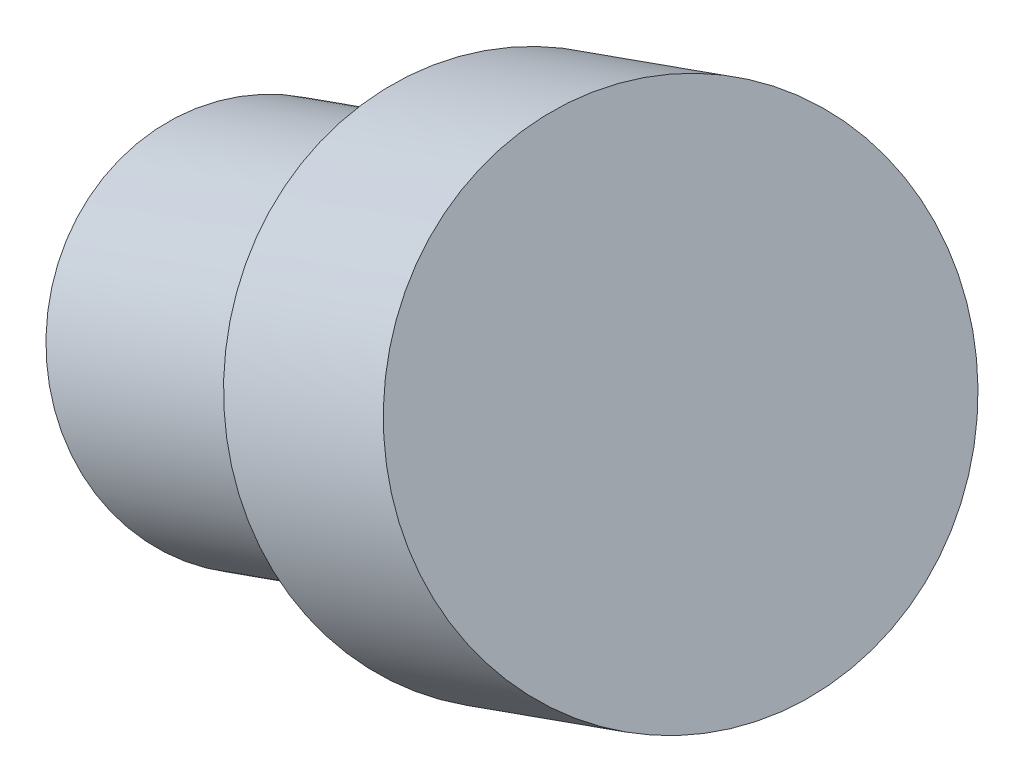
SolidWorks part; units mm, degrees
ref_plane "Front Plane" through (0, 0, 0) normal (0, 0, 1) x (1, 0, 0)
ref_plane "Top Plane" through (0, 0, 0) normal (0, 1, 0) x (1, 0, 0)
ref_plane "Right Plane" through (0, 0, 0) normal (1, 0, 0) x (0, 0, -1)
sketch "Sketch2" plane through (0, 0, 0) normal (0, 1, 0) x (1, 0, 0)
  circle A0 centre (0, 0) radius 32.1849
  point P2 (-33.5264, 9.9443)
extrude "Boss-Extrude1" add sketch "Sketch2" along normal blind 78 contours A0
sketch "Sketch3" plane through (0, 78, 0) normal (0, 1, 0) x (1, 0, 0)
  circle A0 centre (0, 0) radius 44.4528
  point P2 (0, 0)
  point P3 (0, 0)
extrude "Boss-Extrude2" add sketch "Sketch3" along normal blind 48
move or copy body "Body-Move/Copy1" bodies to move or copy 102 copy no translate (-72.9607, 52.2188, 0)
move or copy body "Body-Move/Copy2" bodies to move or copy 103 copy no rotation origin (-95.5514, 86.9316, 17.3344) rotation axis (0.5628, 0.7048, -0.4319) rotation angle 94.867
